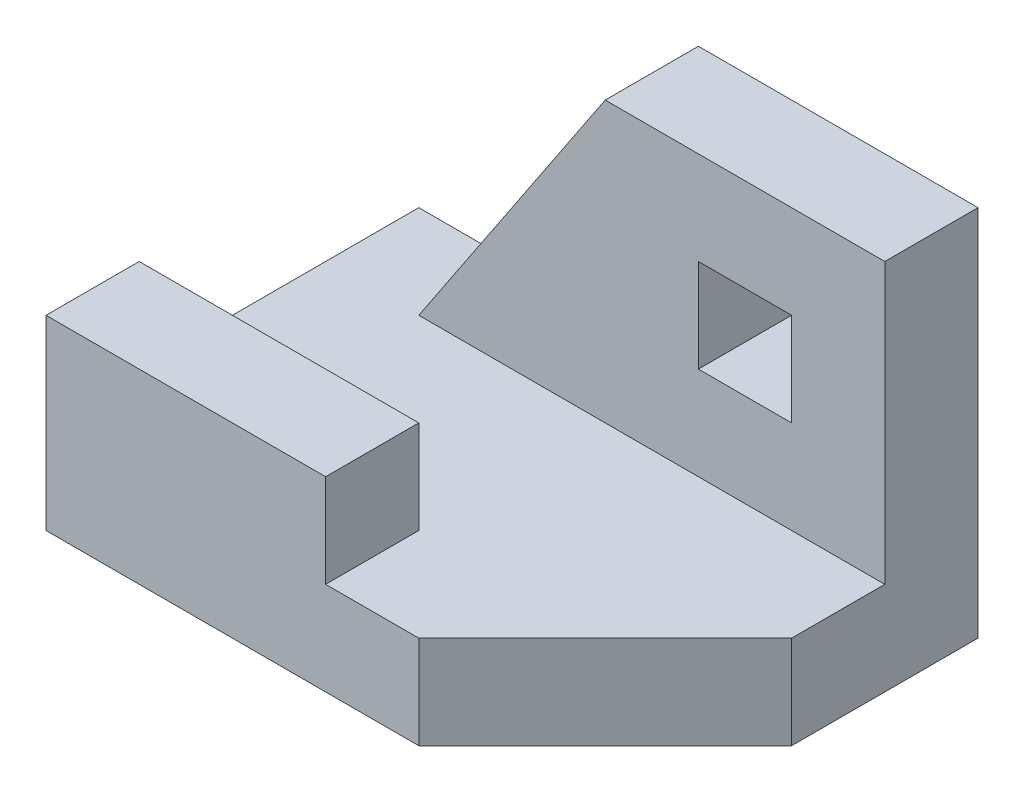
SolidWorks part; units mm, degrees
ref_plane "前基準面" through (0, 0, 0) normal (0, 0, 1) x (1, 0, 0)
ref_plane "上基準面" through (0, 0, 0) normal (0, 1, 0) x (1, 0, 0)
ref_plane "右基準面" through (0, 0, 0) normal (1, 0, 0) x (0, 0, -1)
sketch "草圖1" plane through (0, 0, 0) normal (0, 1, 0) x (1, 0, 0)
  line L0 (20, 0) -> (30, 10)
  line L1 (0, 0) -> (20, 0)
  line L2 (0, 0) -> (0, 20)
  line L3 (0, 20) -> (30, 20)
  line L4 (30, 10) -> (30, 20)
  line L5 (0, 5) -> (15, 5)
  line L6 (15, 5) -> (15, 0)
  line L7 (5, 20) -> (5, 15)
  line L8 (5, 15) -> (30, 15)
  dimension "D1" = 30
  dimension "D2" = 20
  dimension "D3" = 10
  dimension "D4" = 20
  dimension "D5" = 15
  dimension "D6" = 5
  dimension "D7" = 5
  dimension "D8" = 5
extrude "填料-伸長1" add sketch "草圖1" along normal blind 5 contours L7 L8 L4 L3 | L8 L7 L3 L2 L5 L6 L1 L0 L4 | L6 L5 L2 L1 region at (14.0476, 0, -9.881) region at (7.5, 0, -2.5) region at (17.5, 0, -17.5)
extrude "填料-伸長2" add sketch "草圖1<3>" along normal blind 10 contours L6 L5 L2 L1 region at (7.5, 0, -2.5)
sketch "草圖1<3>" plane through (0, 0, 0) normal (0, 1, 0) x (1, 0, 0) same geometry as "草圖1"
extrude "填料-伸長3" add sketch "草圖1<4>" along normal blind 20 contours L7 L8 L4 L3 region at (17.5, 0, -17.5)
sketch "草圖1<4>" plane through (0, 0, 0) normal (0, 1, 0) x (1, 0, 0) same geometry as "草圖1"
sketch "草圖2" plane through (0, 0, -15) normal (0, 0, 1) x (1, 0, 0)
  line L0 (5, 20) -> (30, 20) construction
  line L1 (20, 10) -> (25, 10)
  line L2 (20, 10) -> (20, 15)
  line L3 (20, 15) -> (25, 15)
  line L4 (25, 10) -> (25, 15)
  line L5 (20, 10) -> (25, 15) construction
  line L6 (20, 15) -> (25, 10) construction
  line L7 (30, 20) -> (30, 5) construction
  line L8 (5, 20) -> (15, 20)
  line L9 (15, 20) -> (5, 5)
  line L10 (5, 5) -> (5, 20)
  point P0 (22.5, 12.5)
  dimension "D1" = 5
  dimension "D2" = 5
  dimension "D3" = 5
  dimension "D4" = 5
  dimension "D5" = 10
extrude "除料-伸長1" cut sketch "草圖2" against normal blind 20
